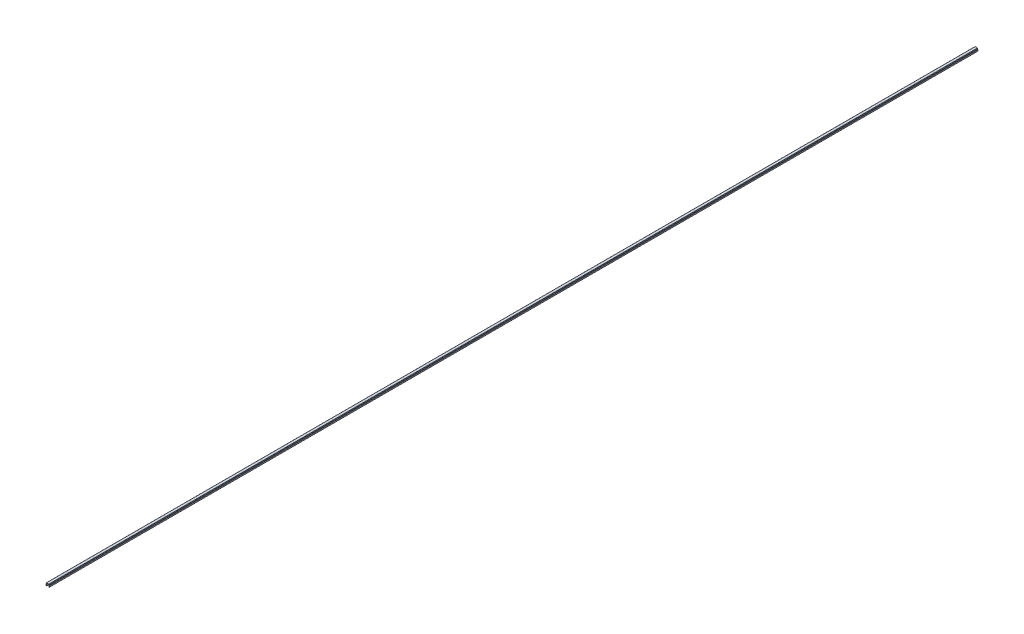
SolidWorks part; units mm, degrees
ref_plane "Front Plane" through (0, 0, 0) normal (0, 0, 1) x (1, 0, 0)
ref_plane "Top Plane" through (0, 0, 0) normal (0, 1, 0) x (1, 0, 0)
ref_plane "Right Plane" through (0, 0, 0) normal (1, 0, 0) x (0, 0, -1)
ref_plane "Plane1" through (0, 0, 0) normal (0, 0, 1) x (1, 0, 0)
sketch "Sketch1" plane through (0, 0, 0) normal (0, 0, 1) x (1, 0, 0)
  line L0 (-3.6, 3.35) -> (-3, 0)
  line L1 (-3, 0) -> (-2.2, 0)
  line L2 (-2.2, 0) -> (-2.7352, 2.9883)
  line L3 (-2.3907, 3.4) -> (-2.2, 3.4)
  line L4 (-2.2, 3.4) -> (-2.0705, 4.8805)
  line L5 (-1.7218, 5.2) -> (1.7218, 5.2)
  line L6 (2.0705, 4.8805) -> (2.2, 3.4)
  line L7 (2.2, 3.4) -> (2.3907, 3.4)
  line L8 (2.7352, 2.9883) -> (2.2, 0)
  line L9 (2.2, 0) -> (3, 0)
  line L10 (3, 0) -> (3.6, 3.35)
  line L11 (3.25, 3.7) -> (3, 3.7)
  line L12 (3, 3.7) -> (2.8355, 5.5805)
  line L13 (2.4868, 5.9) -> (-2.4868, 5.9)
  line L14 (-2.8355, 5.5805) -> (-3, 3.7)
  line L15 (-3, 3.7) -> (-3.25, 3.7)
  arc A0 (-2.7352, 2.9883) -> (-2.3907, 3.4) centre (-2.3907, 3.05) cw
  arc A1 (-2.0705, 4.8805) -> (-1.7218, 5.2) centre (-1.7218, 4.85) cw
  arc A2 (1.7218, 5.2) -> (2.0705, 4.8805) centre (1.7218, 4.85) cw
  arc A3 (2.3907, 3.4) -> (2.7352, 2.9883) centre (2.3907, 3.05) cw
  arc A4 (3.6, 3.35) -> (3.25, 3.7) centre (3.25, 3.35) ccw
  arc A5 (2.8355, 5.5805) -> (2.4868, 5.9) centre (2.4868, 5.55) ccw
  arc A6 (-2.4868, 5.9) -> (-2.8355, 5.5805) centre (-2.4868, 5.55) ccw
  arc A7 (-3.25, 3.7) -> (-3.6, 3.35) centre (-3.25, 3.35) ccw
extrude "Boss-Extrude1" add sketch "Sketch1" against normal blind 1000 and the other way blind 1000
